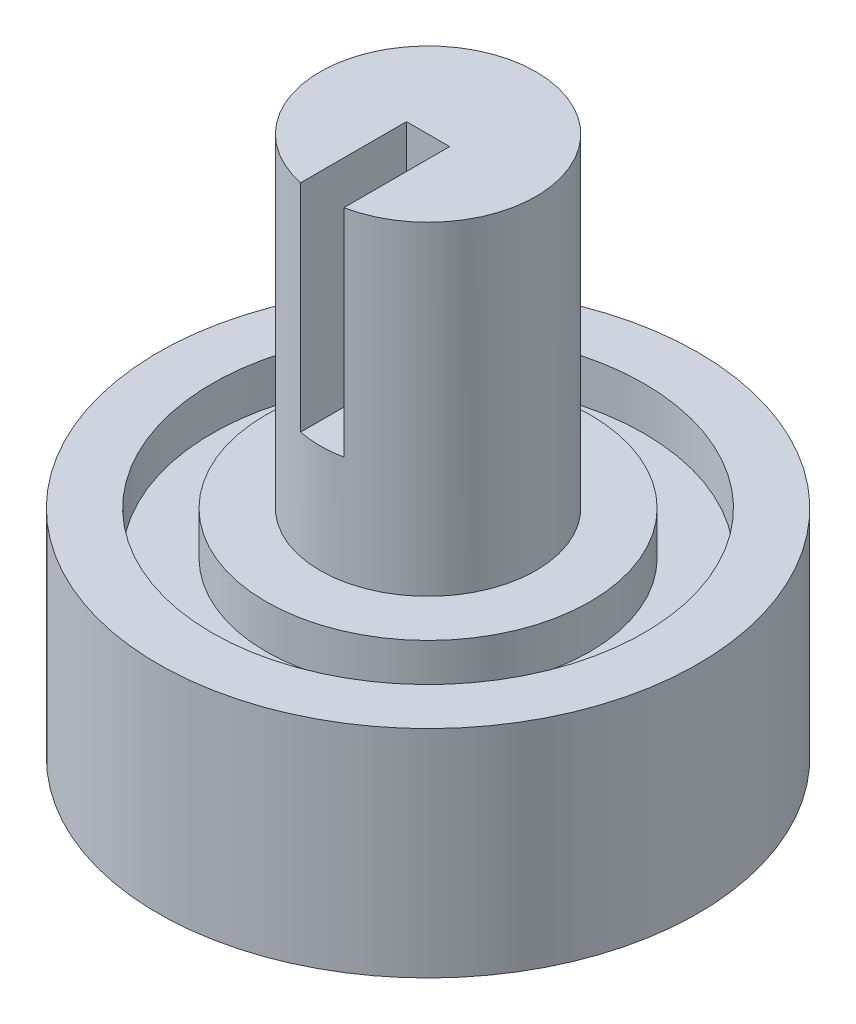
SolidWorks part; units mm, degrees
ref_plane "Front Plane" through (0, 0, 0) normal (0, 0, 1) x (1, 0, 0)
ref_plane "Top Plane" through (0, 0, 0) normal (0, 1, 0) x (1, 0, 0)
ref_plane "Right Plane" through (0, 0, 0) normal (1, 0, 0) x (0, 0, -1)
sketch "Sketch1" plane through (0, 0, 0) normal (0, 0, 1) x (1, 0, 0)
  line L0 (0, 18) -> (0, 0) construction
  line L1 (0, 0) -> (2.5, 0)
  line L2 (2.5, 0) -> (2.5, 4)
  line L3 (2.5, 4) -> (7.5, 4)
  line L4 (7.5, 4) -> (7.5, 6)
  line L5 (7.5, 6) -> (10, 6)
  line L6 (10, 6) -> (10, 4)
  line L7 (10, 4) -> (12.4977, 4)
  line L16 (0, 9) -> (12.4977, 9) construction
  line L17 (12.4977, 4) -> (12.4977, 14)
  line L18 (10, 14) -> (12.4977, 14)
  line L19 (10, 12) -> (10, 14)
  line L20 (7.5, 12) -> (10, 12)
  line L21 (7.5, 14) -> (7.5, 12)
  line L22 (7.5, 14) -> (5, 14)
  line L23 (5, 14) -> (5, 29)
  line L26 (0, 0) -> (0, 29)
  line L27 (0, 29) -> (5, 29)
  point P24 (0, 9)
  dimension "D1" = 15
  dimension "D2" = 20
  dimension "D3" = 2
  dimension "D4" = 5
  dimension "D5" = 5
  dimension "D6" = 4
  dimension "D7" = 12.4977
  dimension "D8" = 15
  dimension "D9" = 5
revolve "Revolve1" add sketch "Sketch1" angle 360 about L26
sketch "Sketch2" plane through (0, 4, 0) normal (0, -1, 0) x (1, 0, 0)
  circle A0 centre (0, 0) radius 3
  dimension "D1" = 6
extrude "Boss-Extrude1" add sketch "Sketch2" along normal blind 1
sketch "Sketch3" plane through (0, 29, 0) normal (0, 1, 0) x (1, 0, 0)
  line L1 (-1, 0) -> (1, 0)
  line L2 (-1, 0) -> (-1, -15.5966)
  line L3 (-1, -15.5966) -> (1, -15.5966)
  line L4 (1, 0) -> (1, -15.5966)
  point P4 (0, 0)
  dimension "D1" = 2
extrude "Cut-Extrude1" cut sketch "Sketch3" against normal blind 10
